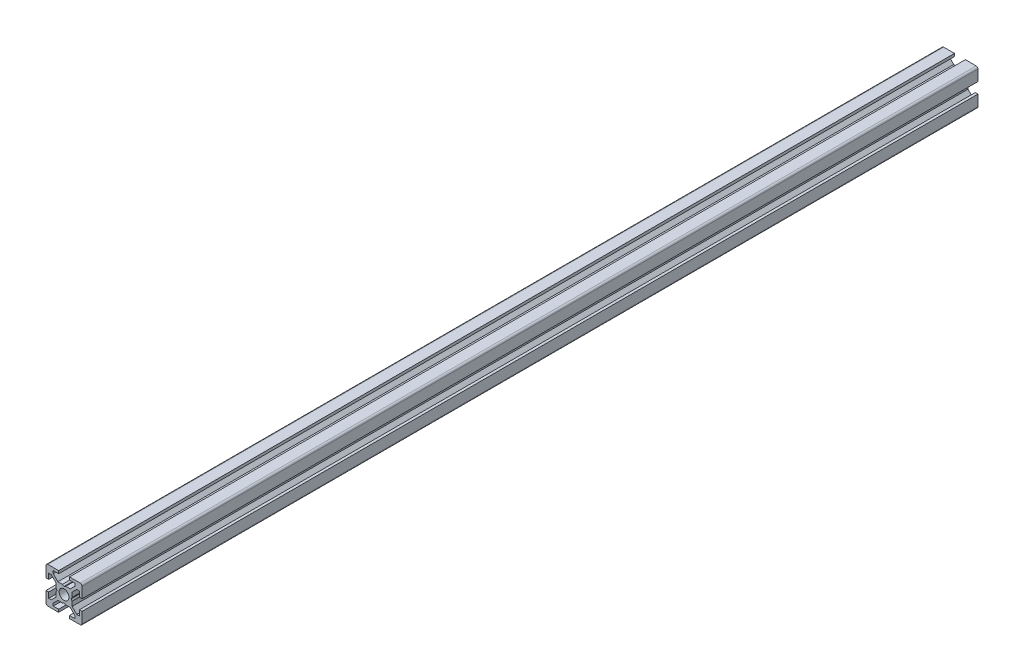
SolidWorks part; units mm, degrees
ref_plane "Front Plane" through (0, 0, 0) normal (0, 0, 1) x (1, 0, 0)
ref_plane "Top Plane" through (0, 0, 0) normal (0, 1, 0) x (1, 0, 0)
ref_plane "Right Plane" through (0, 0, 0) normal (1, 0, 0) x (0, 0, -1)
sketch "Sketch1" plane through (0, 0, 0) normal (0, 0, 1) x (1, 0, 0)
  line L0 (-707.1068, -707.1068) -> (34648.2323, 34648.2323) construction
  line L1 (-3.0018, 10) -> (-10, 10)
  line L2 (0.9376, 4.4579) -> (-0.0011, 3.9339)
  line L3 (3.4252, 4.4579) -> (0.9376, 4.4579)
  line L4 (6.0128, 7.0454) -> (3.4252, 4.4579)
  line L5 (0, -1000) -> (0, 49000) construction
  line L6 (-1000, 0) -> (49000, 0) construction
  line L7 (6.0128, 8.5) -> (6.0128, 7.0454)
  line L8 (3.0018, 8.5) -> (6.0128, 8.5)
  line L9 (3.0018, 10) -> (10, 10)
  line L10 (3.0018, 8.5) -> (3.0018, 10)
  line L11 (-707.1068, 707.1068) -> (34648.2323, -34648.2323) construction
  line L12 (-7.0458, 6.0144) -> (-4.4582, 3.4268)
  line L13 (-8.5008, 6.0144) -> (-7.0458, 6.0144)
  line L14 (-8.5008, 3.0018) -> (-8.5008, 6.0144)
  line L15 (0, -0.0423) -> (0.0002, 2.0704) construction
  line L16 (-10, 3.0018) -> (-10, 10)
  line L17 (-8.5008, 3.0018) -> (-10, 3.0018)
  line L18 (8.5, 3.0018) -> (10, 3.0018)
  line L19 (10, 3.0018) -> (10, 10)
  line L20 (8.5, 3.0018) -> (8.5, 6.0143)
  line L21 (8.5, 6.0143) -> (7.0454, 6.0143)
  line L22 (7.0454, 6.0143) -> (4.4583, 3.4262)
  line L23 (-3.0018, 8.5) -> (-3.0018, 10)
  line L24 (-3.0018, 8.5) -> (-6.0148, 8.5)
  line L25 (-6.0148, 8.5) -> (-6.0148, 7.0458)
  line L26 (-6.0148, 7.0458) -> (-3.4272, 4.4582)
  line L27 (-3.4272, 4.4582) -> (-0.9396, 4.4582)
  line L28 (-0.9396, 4.4582) -> (-0.0011, 3.9339)
  line L29 (-4.4582, 3.4268) -> (-4.4582, 0.9396)
  line L30 (-4.4582, 0.9396) -> (-3.9347, 0)
  line L31 (4.4575, 0.9396) -> (3.9347, 0)
  line L32 (4.4583, 3.4262) -> (4.4575, 0.9396)
  line L37 (-0.9396, -4.4582) -> (-0.0011, -3.9339)
  line L45 (-3.4272, -4.4582) -> (-0.9396, -4.4582)
  line L46 (-6.0148, -7.0458) -> (-3.4272, -4.4582)
  line L47 (-6.0148, -8.5) -> (-6.0148, -7.0458)
  line L48 (-3.0018, -8.5) -> (-6.0148, -8.5)
  line L49 (-3.0018, -10) -> (-10, -10)
  line L50 (-3.0018, -8.5) -> (-3.0018, -10)
  line L51 (4.4588, -0.9386) -> (3.9347, 0)
  line L52 (4.4583, -3.4262) -> (4.4588, -0.9386)
  line L53 (7.0454, -6.0143) -> (4.4583, -3.4262)
  line L54 (8.5, -6.0143) -> (7.0454, -6.0143)
  line L55 (8.5, -3.0018) -> (8.5, -6.0143)
  line L56 (10, -3.0018) -> (10, -10)
  line L57 (8.5, -3.0018) -> (10, -3.0018)
  line L58 (-8.5008, -3.0018) -> (-10, -3.0018)
  line L59 (-10, -3.0018) -> (-10, -10)
  line L60 (-8.5008, -3.0018) -> (-8.5008, -6.0144)
  line L61 (-8.5008, -6.0144) -> (-7.0458, -6.0144)
  line L62 (-7.0458, -6.0144) -> (-4.4582, -3.4268)
  line L63 (-4.4582, -3.4268) -> (-4.4575, -0.9396)
  line L64 (-4.4575, -0.9396) -> (-3.9347, 0)
  line L65 (3.0018, -8.5) -> (3.0018, -10)
  line L66 (3.0018, -10) -> (10, -10)
  line L67 (3.0018, -8.5) -> (6.0128, -8.5)
  line L68 (6.0128, -8.5) -> (6.0128, -7.0454)
  line L69 (6.0128, -7.0454) -> (3.4252, -4.4579)
  line L70 (3.4252, -4.4579) -> (0.9376, -4.4579)
  line L71 (0.9376, -4.4579) -> (-0.0011, -3.9339)
  circle A0 centre (0, 0) radius 2.75
extrude "Boss-Extrude1" add sketch "Sketch1" along normal blind 496
fillet "Fillet2" radius 1 1 edges at (-10, -10, 248) type face fillet first side face at (-10, -6.5009, 248) second side face at (-6.5009, -10, 248)
fillet "Fillet3" radius 1 1 edges at (10, -10, 248) type face fillet first side face at (10, -6.5009, 248) second side face at (6.5009, -10, 248)
fillet "Fillet4" radius 1 1 edges at (-10, 10, 248) type face fillet first side face at (-6.5009, 10, 248) second side face at (-10, 6.5009, 248)
fillet "Fillet5" radius 1 1 edges at (10, 10, 248) type face fillet first side face at (6.5009, 10, 248) second side face at (10, 6.5009, 248)
